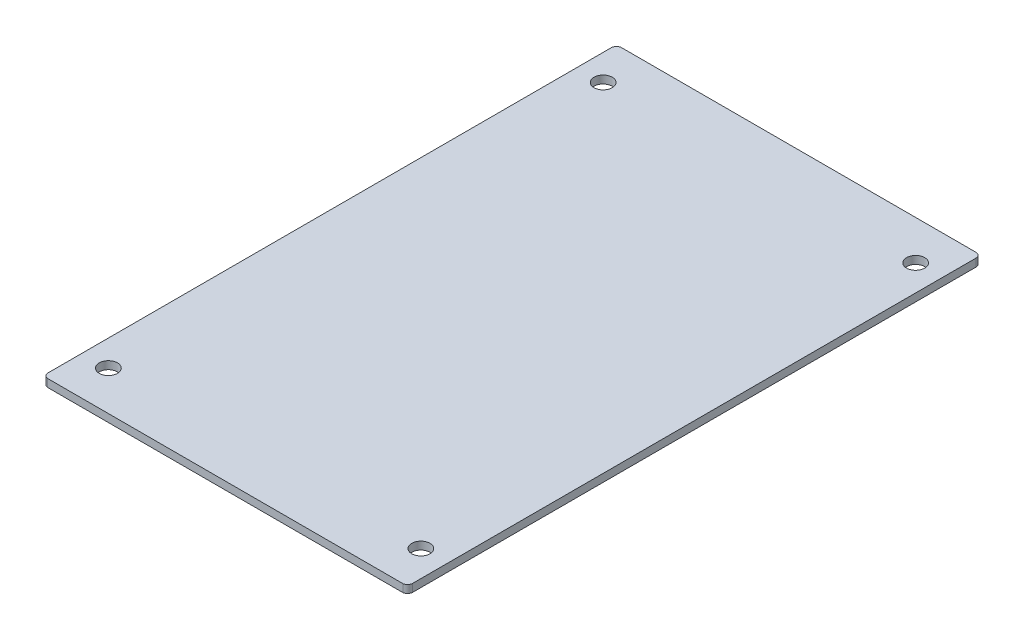
SolidWorks part; units mm, degrees
ref_plane "Front Plane" through (0, 0, 0) normal (0, 0, 1) x (1, 0, 0)
ref_plane "Top Plane" through (0, 0, 0) normal (0, 1, 0) x (1, 0, 0)
ref_plane "Right Plane" through (0, 0, 0) normal (1, 0, 0) x (0, 0, -1)
sketch "Sketch1" plane through (0, 0, 0) normal (0, 1, 0) x (1, 0, 0)
  line L0 (0, 55) -> (0, 132) construction
  line L1 (-35, -55) -> (-28, -55)
  line L2 (-35, -55) -> (-35, 55)
  line L3 (-35, 55) -> (-28, 55)
  line L4 (35, -55) -> (35, 55)
  line L5 (-35, -55) -> (35, 55) construction
  line L6 (-35, 55) -> (35, -55) construction
  line L7 (-30, -47.5) -> (30, -47.5) construction
  line L8 (-30, -47.5) -> (-30, 47.5) construction
  line L9 (-30, 47.5) -> (30, 47.5) construction
  line L10 (30, -47.5) -> (30, 47.5) construction
  line L11 (-30, -47.5) -> (30, 47.5) construction
  line L12 (-30, 47.5) -> (30, -47.5) construction
  line L13 (-28, 132) -> (28, 132) construction
  line L14 (0, 0) -> (-35, 0) construction
  line L15 (-28, 132) -> (-28, 55)
  line L16 (28, 132) -> (28, 55)
  line L17 (28, -132) -> (28, -55)
  line L18 (-28, -132) -> (28, -132) construction
  line L19 (-28, -132) -> (-28, -55)
  line L20 (-28, -55) -> (28, -55) construction
  line L21 (28, -55) -> (35, -55)
  line L22 (0, 55) -> (28, 55) construction
  line L23 (28, 55) -> (35, 55)
  line L24 (-28, 55) -> (0, 55) construction
  line L25 (28, 132) -> (0, 144)
  line L26 (0, 144) -> (-28, 132)
  line L27 (0, -144) -> (-28, -132)
  line L28 (28, -132) -> (0, -144)
  circle A0 centre (-30, 47.5) radius 1.75
  circle A1 centre (30, 47.5) radius 1.75
  circle A2 centre (30, -47.5) radius 1.75
  circle A3 centre (-30, -47.5) radius 1.75
  point P0 (0, 0)
  point P6 (0, 0)
  point P20 (0, 132)
  dimension "D3" = 3.5
  dimension "D1" = 70
  dimension "D2" = 110
  dimension "D4" = 7.5
  dimension "D5" = 5
  dimension "D6" = 56
  dimension "D7" = 264
  dimension "D8" = 12
extrude "Boss-Extrude1" add sketch "Sketch1" along normal blind 1.5
fillet "Fillet1" radius 7 4 edges at (-28, 0.75, 55) (28, 0.75, 55) (28, 0.75, -55) (-28, 0.75, -55)
fillet "Fillet2" radius 1 4 edges at (35, 0.75, -55) (35, 0.75, 55) (-35, 0.75, 55) (-35, 0.75, -55)
fillet "Fillet3" radius 50 2 edges at (0, 0.75, 144) (0, 0.75, -144)
sketch "Sketch2" plane through (0, 1.5, 0) normal (0, 1, 0) x (1, 0, 0)
  line L1 (34.125, 55.0549) -> (-69.2776, 55.0549)
  line L2 (34.125, 55.0549) -> (34.125, 160.835)
  line L3 (34.125, 160.835) -> (-69.2776, 160.835)
  line L4 (-69.2776, 55.0549) -> (-69.2776, 160.835)
extrude "Cut-Extrude1" cut sketch "Sketch2" against normal blind 10
mirror "Mirror1" about plane through (0, 0, 0) normal (0, 0, 1) of "Cut-Extrude1"
